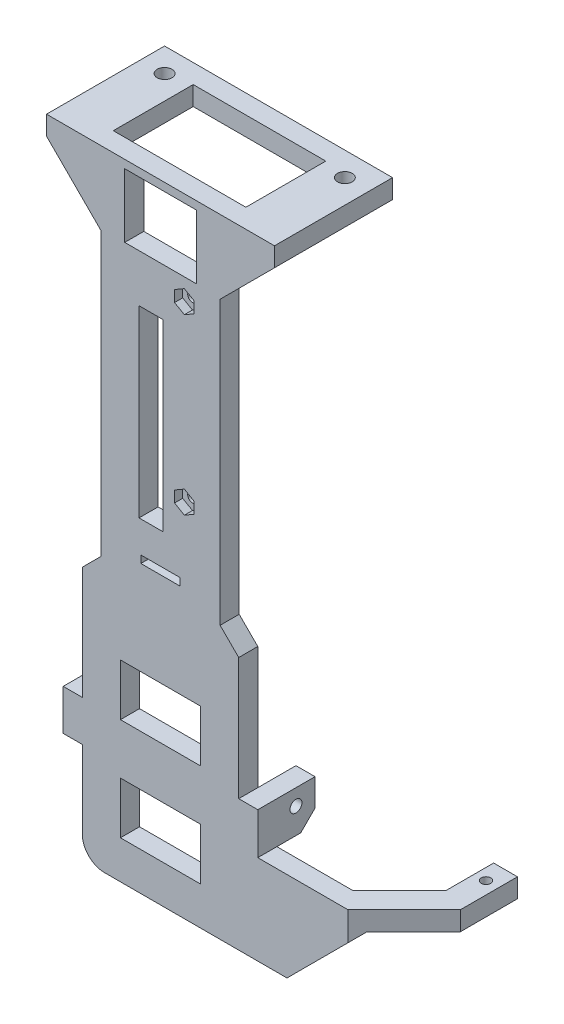
SolidWorks part; units mm, degrees
ref_plane "前视基准面" through (0, 0, 0) normal (0, 0, 1) x (1, 0, 0)
ref_plane "上视基准面" through (0, 0, 0) normal (0, 1, 0) x (1, 0, 0)
ref_plane "右视基准面" through (0, 0, 0) normal (1, 0, 0) x (0, 0, -1)
other "Configuration Table"
sketch "草图1" plane through (0, 0, 0) normal (0, 0, 1) x (1, 0, 0)
  line L1 (-16.4, -7.25) -> (16.4, -7.25)
  line L2 (-16.4, -7.25) -> (-16.4, 119.75)
  line L3 (-16.4, 119.75) -> (16.4, 119.75)
  line L4 (16.4, -7.25) -> (16.4, 119.75)
  line L20 (-16.4, 3.05) -> (-16.4, -7.25)
  line L21 (-11.75, -11.9) -> (11.75, -11.9)
  line L22 (16.4, -7.25) -> (16.4, 31.75)
  line L23 (11.75, 36.4) -> (-11.75, 36.4)
  line L39 (-16.4, 3.05) -> (-16.4, -7.25)
  line L40 (-11.75, -11.9) -> (11.75, -11.9)
  line L41 (16.4, -7.25) -> (16.4, 31.75)
  line L42 (11.75, 36.4) -> (-11.75, 36.4)
  line L135 (-13.4, 3.05) -> (-16.4, 3.05)
  line L136 (-16.0375, 33.55) -> (-11.75, 33.55)
  line L137 (-11.75, 33.55) -> (-11.75, 33.4)
  line L138 (-11.75, 33.4) -> (11.75, 33.4)
  line L139 (13.4, 31.75) -> (13.4, 17.25)
  line L140 (11.75, 15.6) -> (-11.75, 15.6)
  line L141 (-13.4, 17.25) -> (-13.4, 27.55)
  line L142 (-13.4, 27.55) -> (-16.4, 27.55)
  line L143 (-16.4, 27.55) -> (-16.4, 9.05)
  line L144 (-16.4, 27.55) -> (-16.4, 9.05)
  line L145 (-16.4, 9.05) -> (-11.75, 9.05)
  line L146 (-11.75, 9.05) -> (-11.75, 8.9)
  line L147 (-11.75, 8.9) -> (11.75, 8.9)
  line L148 (13.4, 7.25) -> (13.4, -7.25)
  line L149 (11.75, -8.9) -> (-11.75, -8.9)
  line L150 (-13.4, -7.25) -> (-13.4, 3.05)
  line L521 (-18.9, 31.75) -> (-16.4, 31.75) construction
  arc A10 (-16.4, -7.25) -> (-11.75, -11.9) centre (-11.75, -7.25) ccw
  arc A11 (11.75, -11.9) -> (16.4, -7.25) centre (11.75, -7.25) ccw
  arc A12 (16.4, 31.75) -> (11.75, 36.4) centre (11.75, 31.75) ccw
  arc A13 (-11.75, 36.4) -> (-16.0375, 33.55) centre (-11.75, 31.75) ccw
  arc A20 (-16.4, -7.25) -> (-11.75, -11.9) centre (-11.75, -7.25) ccw
  arc A21 (11.75, -11.9) -> (16.4, -7.25) centre (11.75, -7.25) ccw
  arc A22 (16.4, 31.75) -> (11.75, 36.4) centre (11.75, 31.75) ccw
  arc A76 (13.4, 31.75) -> (11.75, 33.4) centre (11.75, 31.75) ccw
  arc A77 (11.75, 15.6) -> (13.4, 17.25) centre (11.75, 17.25) ccw
  arc A78 (-13.4, 17.25) -> (-11.75, 15.6) centre (-11.75, 17.25) ccw
  arc A79 (13.4, 7.25) -> (11.75, 8.9) centre (11.75, 7.25) ccw
  arc A80 (11.75, -8.9) -> (13.4, -7.25) centre (11.75, -7.25) ccw
  arc A81 (-13.4, -7.25) -> (-11.75, -8.9) centre (-11.75, -7.25) ccw
  arc A280 (-11.75, 36.4) -> (-16.0375, 33.55) centre (-11.75, 31.75) ccw construction
  arc A281 (-11.75, 36.4) -> (-16.4, 31.75) centre (-11.75, 31.75) ccw
  arc A282 (-16.2146, 33.05) -> (-16.4, 31.75) centre (-11.75, 31.75) ccw construction
  dimension "D2" = 2
  dimension "D1" = 0
extrude "凸台-拉伸1" add sketch "草图1" along normal blind 4
sketch "草图2" plane through (0, 0, 0) normal (0, 0, -1) x (-1, 0, 0)
  line L0 (7, 117.55) -> (-7, 117.55) construction
  line L1 (-8.5, 104.6634) -> (7.5, 104.6634) construction
  line L3 (-7.5, 104.6634) -> (7.5, 104.6634)
  line L4 (16.4, -7.25) -> (16.4, 119.75)
  line L5 (16.4, 119.75) -> (-16.4, 119.75)
  line L7 (16.4, -7.25) -> (16.4, 119.75)
  line L9 (16.4, 119.75) -> (-16.4, 119.75)
  line L12 (-7.5, 104.6634) -> (-7.5, 118.05)
  line L13 (-7.5, 118.05) -> (7.5, 118.05)
  line L14 (7.5, 104.6634) -> (7.5, 118.05)
  line L15 (7.5, 107.05) -> (7.5, 117.05) construction
  line L16 (-7.5, 117.05) -> (-7.5, 107.05) construction
  line L22 (-16.4, 119.75) -> (-16.4, -7.25)
  line L24 (-16.4, 119.75) -> (-16.4, -7.25)
  line L25 (-11.75, -11.9) -> (11.75, -11.9)
  line L26 (-11.75, -11.9) -> (11.75, -11.9)
  arc A2 (-16.4, -7.25) -> (-11.75, -11.9) centre (-11.75, -7.25) ccw
  arc A3 (-16.4, -7.25) -> (-11.75, -11.9) centre (-11.75, -7.25) ccw
  arc A6 (11.75, -11.9) -> (16.4, -7.25) centre (11.75, -7.25) ccw
  arc A7 (11.75, -11.9) -> (16.4, -7.25) centre (11.75, -7.25) ccw
  dimension "D2" = 0
  dimension "D3" = 0
  dimension "D4" = 0.5
  dimension "D1" = 0
extrude "切除-拉伸1" cut sketch "草图2" against normal through all contours L3 L14 L9 L12
sketch "草图3" plane through (0, 119.75, 0) normal (0, 1, 0) x (1, 0, 0)
  line L1 (-23.9, 20.755) -> (-13.9, 20.755)
  line L2 (-23.9, 20.755) -> (-23.9, 10.755)
  line L3 (-23.9, 10.755) -> (-13.9, 10.755)
  line L4 (-13.9, 20.755) -> (-13.9, 10.755)
  line L5 (-23.9, 20.755) -> (-13.9, 10.755) construction
  line L6 (-23.9, 10.755) -> (-13.9, 20.755) construction
  line L11 (-23.9, 10.755) -> (-13.9, 10.755)
  line L12 (-23.9, 10.755) -> (-23.9, -4)
  line L13 (-23.9, -4) -> (-13.9, -4)
  line L14 (-13.9, 10.755) -> (-13.9, -4)
  line L15 (-16.4, -4) -> (16.4, -4) construction
  circle A0 centre (-18.9, 15.755) radius 1.5 construction
  circle A2 centre (-18.9, 15.755) radius 1.55
  point P0 (-18.9, 15.755)
  dimension "D1" = 3.1
  dimension "D3" = 10
  dimension "D5" = 10
extrude "凸台-拉伸2" add sketch "草图3" against normal blind 4
mirror "镜向1" about plane through (0, 0, 0) normal (1, 0, 0) of "凸台-拉伸2"
sketch "草图5" plane through (0, 2.8903, 0) normal (0, 1, 0) x (1, 0, 0)
  line L0 (46.0958, 21.655) -> (46.0958, 9.855) construction
  line L1 (46.0958, 19.755) -> (51.0958, 19.755)
  line L2 (46.0958, 19.755) -> (46.0958, 9.855)
  line L3 (46.0958, 9.855) -> (51.0958, 9.855)
  line L4 (51.0958, 19.755) -> (51.0958, 9.855)
  line L5 (21.055, 19.755) -> (23.5958, 19.755) construction
  line L10 (50.7958, 9.855) -> (46.0958, 9.855) construction
  line L11 (46.0958, 9.855) -> (32.2408, -4)
  line L12 (51.0958, 9.855) -> (51.0958, 7.7839)
  line L13 (51.0958, 7.7839) -> (39.3118, -4)
  line L14 (32.2408, -4) -> (39.3118, -4)
  line L19 (-23.9, -4) -> (23.9, -4) construction
  arc A0 (49.2557, 16.405) -> (49.2557, 15.105) centre (48.4958, 15.755) ccw construction
  circle A1 centre (48.4958, 15.755) radius 1
  line M5 (50.7958, 9.855) -> (50.7958, 15.105)
  line M6 (50.7958, 15.105) -> (49.2557, 15.105)
  arc M7 (49.2557, 15.105) -> (49.2557, 16.405) centre (48.4958, 15.755) cw
  line M8 (49.2557, 16.405) -> (50.7958, 16.405)
  line M9 (50.7958, 16.405) -> (50.7958, 21.655)
  line M11 (46.0958, 21.655) -> (46.0958, 9.855)
  line M12 (46.0958, 9.855) -> (50.7958, 9.855)
  dimension "D1" = 5
  dimension "D2" = 135
  dimension "D3" = 5
extrude "凸台-拉伸3" add sketch "草图5" along normal blind 4 separate body contours L11 L14 L13 L12 L3 M12 | L1 M11 M12 M5 M6 M7 M8 M9 | A1 L3 L4 L1 M6 M5 M9 M8
sketch "草图6" plane through (0, 0, 4) normal (0, 0, 1) x (1, 0, 0)
  line L10 (-23.9, 115.75) -> (-16.4, 108.25)
  line L11 (-16.4, -7.25) -> (-16.4, 115.75) construction
  line L12 (16.4, 108.25) -> (23.9, 115.75)
  line L13 (16.4, -7.25) -> (16.4, 115.75) construction
  line L14 (23.9, 115.75) -> (16.4, 115.75) construction
  line L15 (-23.9, 115.75) -> (-16.4, 115.75) construction
  line M14 (16.4, 115.75) -> (23.9, 115.75)
  line M18 (-23.9, 115.75) -> (-16.4, 115.75)
  line M22 (-16.4, 115.75) -> (-16.4, -7.25)
  line M24 (16.4, -7.25) -> (16.4, 115.75)
  dimension "D1" = 45
  dimension "D2" = 45
extrude "凸台-拉伸4" add sketch "草图6" against normal up to surface (4 mm away) contours L10 M18 M22 | L12 M24 M14 up to face at (0, 111.3567, 0)
sketch "草图7" plane through (0, 119.75, 0) normal (0, 1, 0) x (1, 0, 0)
  line L0 (13.9, 20.755) -> (13.9, 0) construction
  line L1 (-13.9, 20.755) -> (13.9, 20.755)
  line L2 (-13.9, 20.755) -> (-13.9, 16.755)
  line L3 (-13.9, 16.755) -> (13.9, 16.755)
  line L4 (13.9, 20.755) -> (13.9, 16.755)
  dimension "D1" = 4
extrude "凸台-拉伸5" add sketch "草图7" against normal blind 4
sketch "草图8" plane through (0, 0, 4) normal (0, 0, 1) x (1, 0, 0)
  line L0 (39.3118, 0.8903) -> (26.5215, -11.9)
  line L1 (11.75, -11.9) -> (39.3118, -11.9)
  line L2 (11.75, -11.9) -> (11.75, 6.8903)
  line L3 (11.75, 6.8903) -> (39.3118, 6.8903)
  line L4 (39.3118, -11.9) -> (39.3118, 6.8903)
  line L5 (51.0958, 2.8903) -> (39.3118, 2.8903) construction
  line M1 (16.4, -7.25) -> (16.4, 108.25)
  arc M10 (11.75, -11.9) -> (16.4, -7.25) centre (11.75, -7.25) ccw
  dimension "D1" = 45
  dimension "D2" = 2
extrude "凸台-拉伸6" add sketch "草图8" against normal blind 4 contours L0 L4 L3 L1 M1 M10
sketch "草图11" plane through (0, 0, 4) normal (0, 0, 1) x (1, 0, 0)
  line L1 (-8.4, -3.9) -> (8.4, -3.9)
  line L2 (-8.4, -3.9) -> (-8.4, 28.4)
  line L3 (-8.4, 28.4) -> (8.4, 28.4)
  line L4 (8.4, -3.9) -> (8.4, 28.4)
  line L7 (11.75, 36.4) -> (-11.75, 36.4) construction
  line L8 (-13.45, 15.55) -> (13.45, 15.55) construction
  line L9 (16.4, 8.95) -> (-13.45, 8.95) construction
  line L10 (-13.45, 15.55) -> (13.45, 15.55)
  line L11 (16.4, 8.95) -> (-13.45, 8.95)
  line L12 (-8.4, 6.95) -> (8.4, 6.95)
  line L13 (-8.4, 17.55) -> (8.4, 17.55)
  line L14 (-16.4, -7.25) -> (-16.4, 3.05) construction
  line L15 (-11.75, -11.9) -> (11.75, -11.9) construction
  line L16 (16.4, -7.25) -> (16.4, 31.75) construction
  dimension "D1" = 8
  dimension "D2" = 8
  dimension "D3" = 8
  dimension "D4" = 8
  dimension "D5" = 2
  dimension "D6" = 2
extrude "切除-拉伸2" cut sketch "草图11" against normal through all contours L4 L11 L2 L1 | L2 L10 L4 L3
chamfer "倒角1" distance 2 angle 45 1 edges at (39.3118, 2.8903, 2)
chamfer "倒角2" distance 2 angle 45 1 edges at (38.7763, 2.8903, 0)
sketch "草图12" plane through (-16.4, 0, 0) normal (-1, 0, 0) x (0, 0, 1)
  line L0 (4, -7.25) -> (4, 108.25) construction
  line L1 (4, 9.05) -> (-8, 9.05)
  line L2 (4, 9.05) -> (4, 17.6)
  line L3 (4, 17.6) -> (-8, 17.6)
  line L4 (-8, 9.05) -> (-8, 17.6)
  line L5 (0, 9.05) -> (-4, 9.05) construction
  line L7 (-11.22, 15.6) -> (0, 15.6) construction
  circle A0 centre (-4, 12.25) radius 1.1 construction
  circle A1 centre (-4, 12.25) radius 1.25
  dimension "D2" = 4
  dimension "D3" = 2.5
  dimension "D1" = 2
extrude "凸台-拉伸7" add sketch "草图12" along normal blind 4
sketch "草图13" plane through (16.4, 0, 0) normal (1, 0, 0) x (0, 0, -1)
  line L0 (8, 17.6) -> (8, 9.05) construction
  line L1 (8, 15.6) -> (-4, 15.6)
  line L2 (8, 15.6) -> (8, 6.8903)
  line L3 (8, 6.8903) -> (-4, 6.8903)
  line L4 (-4, 15.6) -> (-4, 6.8903)
  line L6 (11.22, 15.6) -> (0, 15.6) construction
  line L7 (8, 9.8903) -> (5, 6.8903)
  circle A0 centre (4, 12.25) radius 1.25
  line M5 (-4, 6.8903) -> (0, 6.8903)
  line M6 (0, 6.8903) -> (0, 108.25)
  line M8 (-4, 108.25) -> (-4, 6.8903)
  dimension "D1" = 2.5
  dimension "D2" = 45
  dimension "D3" = 3
extrude "凸台-拉伸8" add sketch "草图13" along normal blind 4 contours L7 L2 L1 L3 A0 M6 | L1 M6 M8 M5
sketch "草图14" plane through (0, 0, 0) normal (0, 0, -1) x (-1, 0, 0)
  circle A0 centre (-5, 63.75) radius 1
  circle A1 centre (-5, 100.15) radius 1
  dimension "D1" = 2
  dimension "D2" = 2
extrude "切除-拉伸3" cut sketch "草图14" against normal through all
sketch "草图15" plane through (0, 0, 0) normal (0, 0, -1) x (-1, 0, 0)
  line L2 (-7.3255, 59.13) -> (-1.7519, 59.13) construction
  line L3 (-6, 59.9129) -> (-6, 58.3471) construction
  line L4 (-5.9, 58.4095) -> (-5.9, 60.3997) construction
  circle A2 centre (-5, 95.5) radius 0.9
  circle A3 centre (-5, 95.5) radius 1 construction
  circle A4 centre (-5, 59.13) radius 0.9
  point P9 (-6, 59.13)
  dimension "D1" = 0.1
  dimension "D2" = 0.1
extrude "凸台-拉伸9" add sketch "草图15" along normal blind 1
fillet "圆角1" radius 0.9 2 edges at (4.1, 59.13, -1) (4.1, 95.5, -1)
sketch "草图16" plane through (0, 0, 4) normal (0, 0, 1) x (1, 0, 0)
  line L1 (5, 66.1171) -> (2.95, 64.9336)
  line L2 (2.95, 64.9336) -> (2.95, 62.5664)
  line L3 (2.95, 62.5664) -> (5, 61.3829)
  line L4 (5, 61.3829) -> (7.05, 62.5664)
  line L5 (7.05, 62.5664) -> (7.05, 64.9336)
  line L6 (7.05, 64.9336) -> (5, 66.1171)
  line L7 (7.05, 98.9664) -> (7.05, 101.3336)
  line L8 (7.05, 101.3336) -> (5, 102.5171)
  line L9 (5, 102.5171) -> (2.95, 101.3336)
  line L10 (2.95, 101.3336) -> (2.95, 98.9664)
  line L11 (2.95, 98.9664) -> (5, 97.7829)
  line L12 (5, 97.7829) -> (7.05, 98.9664)
  circle A0 centre (5, 63.75) radius 2.05 construction
  circle A1 centre (5, 100.15) radius 2.05 construction
  point P10 (2.9454, 98.9745)
  point P19 (3.5138, 98.3075)
  circle M13 centre (5, 63.75) radius 1
  circle M14 centre (5, 100.15) radius 1
  dimension "D1" = 4.1
extrude "切除-拉伸4" cut sketch "草图16" against normal blind 1.7 contours L5 L6 L1 L2 L3 L4 M13 | L11 L12 L7 L8 L9 L10 M14
sketch "草图17" plane through (0, 0, 0) normal (0, 0, -1) x (-1, 0, 0)
  line L0 (-16.4, 108.25) -> (-12.5, 104.35)
  line L5 (-12.5, 104.35) -> (-12.5, 45.1366)
  line L6 (-12.5, 45.1366) -> (-16.4, 41.2366)
  line L7 (-16.4, 15.6) -> (-16.4, 108.25) construction
  line L9 (-8.5, 104.6634) -> (-8.5, 50.1366) construction
  line L10 (-23.9, 115.75) -> (-16.4, 108.25) construction
  line L11 (7.4581, 50.1366) -> (-8.5, 50.1366) construction
  line M28 (-16.4, 108.25) -> (-16.4, 15.6)
  dimension "D1" = 4
  dimension "D2" = 135
  dimension "D3" = 5
extrude "切除-拉伸5" cut sketch "草图17" against normal through all and the other way through all contours L6 L5 L0 M28
mirror "镜向2" about plane through (0, 0, 0) normal (1, 0, 0) of "切除-拉伸5"
sketch "草图19" plane through (0, 0, 0) normal (0, 0, -1) x (-1, 0, 0)
  line L4 (-7.5, 104.6634) -> (7.5, 104.6634) construction
  line L5 (4.5, 56.1366) -> (-0.5, 56.1366)
  line L6 (4.5, 56.1366) -> (4.5, 94.6634)
  line L7 (4.5, 94.6634) -> (-0.5, 94.6634)
  line L8 (-0.5, 56.1366) -> (-0.5, 94.6634)
  line L9 (7.4581, 50.1366) -> (-8.5, 50.1366) construction
  line L10 (7.5, 50.2029) -> (7.5, 104.6634) construction
  line L11 (0, 49.4) -> (-4.2426, 49.4) construction
  line L12 (-4.1184, 48.25) -> (4.1184, 48.25) construction
  line L13 (0, 49.4) -> (-4.2426, 49.4)
  line L14 (-4.1184, 48.25) -> (4.1184, 48.25)
  line L16 (-4.1184, 49.6) -> (4.1184, 49.6)
  line L17 (-4.1184, 49.6) -> (-4.1184, 48.05)
  line L18 (-4.1184, 48.05) -> (4.1184, 48.05)
  line L19 (4.1184, 49.6) -> (4.1184, 48.05)
  point P18 (0, 0)
  point P19 (0, 0)
  dimension "D1" = 10
  dimension "D2" = 6
  dimension "D3" = 3
  dimension "D4" = 5
  dimension "D5" = 0.2
  dimension "D6" = 0.2
extrude "切除-拉伸6" cut sketch "草图19" against normal through all
equation "\"axis_fixing_hole\"= 3.1"
equation "\"axis_sliding_hole\"= 3.1"
equation "\"D1@草图3\"=\"axis_fixing_hole\""
